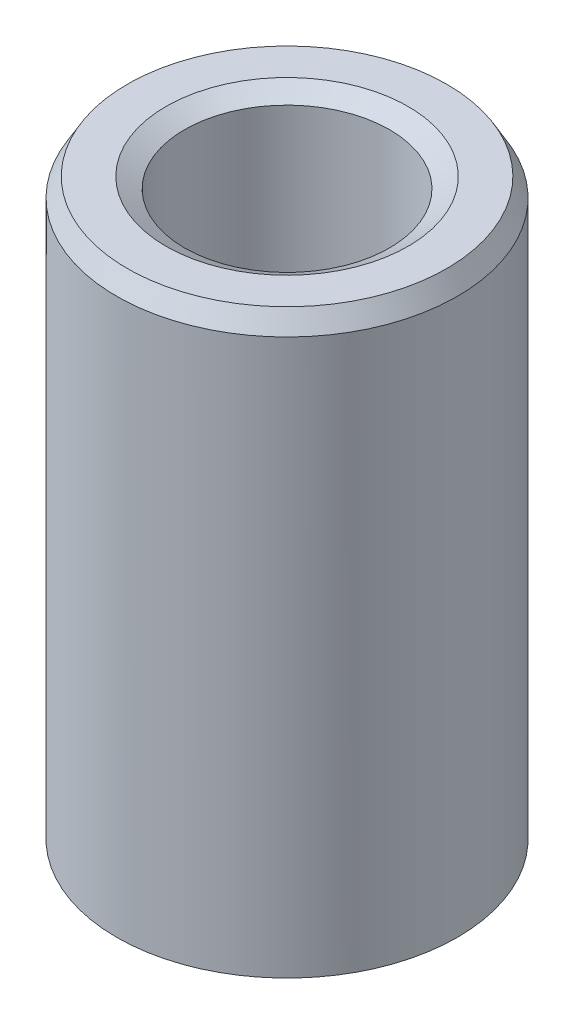
SolidWorks part; units mm, degrees
ref_plane "Front Plane" through (0, 0, 0) normal (0, 0, 1) x (1, 0, 0)
ref_plane "Top Plane" through (0, 0, 0) normal (0, 1, 0) x (1, 0, 0)
ref_plane "Right Plane" through (0, 0, 0) normal (1, 0, 0) x (0, 0, -1)
sketch "Sketch1" plane through (0, 0, 0) normal (0, 1, 0) x (1, 0, 0)
  circle A0 centre (0, 0) radius 32.5
  dimension "SLEEVE_OD" = 65
extrude "Boss-Extrude1" add sketch "Sketch1" along normal blind 111.4651
sketch "Sketch2" plane through (0, 0, 0) normal (0, 1, 0) x (1, 0, 0)
  circle A0 centre (0, 0) radius 19.5449
  dimension "BORE_D" = 39.0899
extrude "Cut-Extrude1" cut sketch "Sketch2" along normal through all
chamfer "Chamfer1" distance 3.549 angle 30 4 edges at (0, 111.4651, 19.5449) (0, 0, 19.5449) (0, 0, 32.5) (0, 111.4651, 32.5) first distance on face at (0, 111.4651, 19.5449) first distance on face at (0, 0, 19.5449) first distance on face at (0, 111.4651, 32.5)
